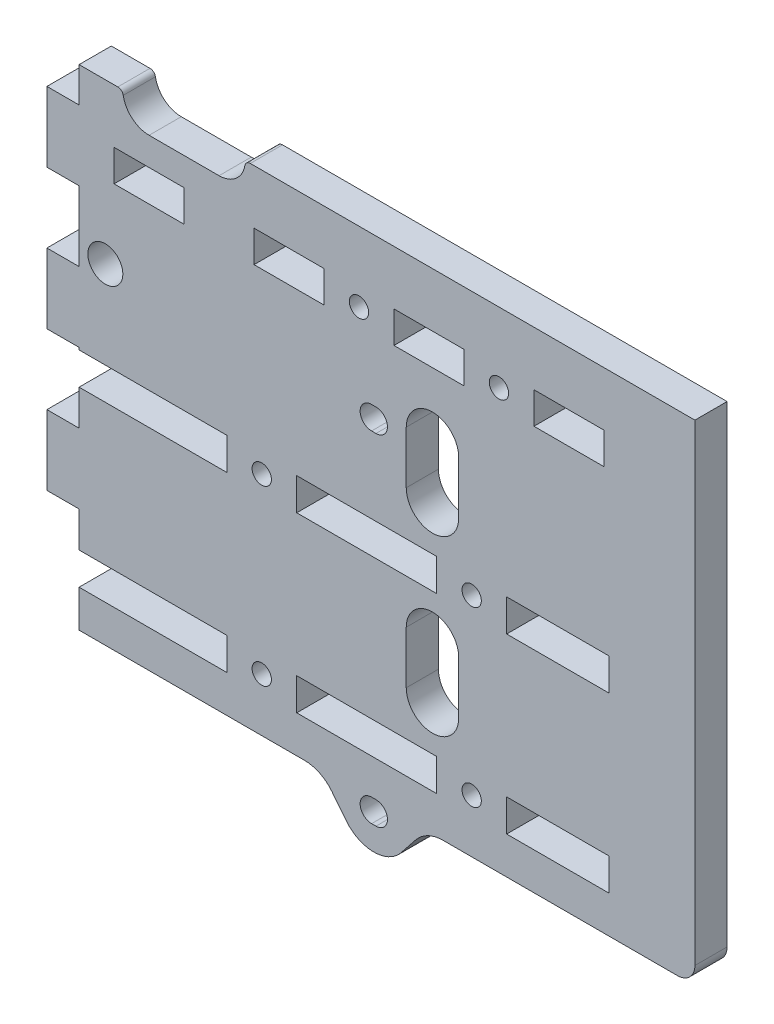
SolidWorks part; units mm, degrees
ref_plane "Front Plane" through (0, 0, 0) normal (0, 0, 1) x (1, 0, 0)
ref_plane "Top Plane" through (0, 0, 0) normal (0, 1, 0) x (1, 0, 0)
ref_plane "Right Plane" through (0, 0, 0) normal (1, 0, 0) x (0, 0, -1)
sketch "Sketch1" plane through (0, 0, 0) normal (0, 0, 1) x (1, 0, 0)
  line L0 (-61.722, 0) -> (-61.722, 12.7)
  line L1 (55.88, -44.45) -> (7.1279, -44.45)
  line L2 (55.88, -44.45) -> (55.88, 44.45)
  line L3 (55.88, 44.45) -> (-55.88, 44.45)
  line L4 (-55.88, -44.45) -> (-55.88, -37.692)
  line L5 (55.88, -44.45) -> (-55.88, 44.45) construction
  line L6 (55.88, 44.45) -> (-55.88, -44.45) construction
  line L7 (-61.722, 25.4) -> (-55.88, 25.4)
  line L8 (-61.722, 25.4) -> (-61.722, 38.1)
  line L9 (-61.722, 38.1) -> (-55.88, 38.1)
  line L10 (-55.88, 12.7) -> (-55.88, 25.4)
  line L11 (-61.722, 25.4) -> (-55.88, 38.1) construction
  line L12 (-61.722, 38.1) -> (-55.88, 25.4) construction
  line L13 (-61.722, 12.7) -> (-55.88, 12.7)
  line L14 (-61.722, 0) -> (-55.88, 0)
  line L15 (-61.722, -25.4) -> (-61.722, -12.7)
  line L16 (-61.722, -12.7) -> (-55.88, -12.7)
  line L17 (-61.722, -25.4) -> (-55.88, -25.4)
  line L18 (-61.722, 12.7) -> (-55.88, 0) construction
  line L19 (-61.722, 0) -> (-55.88, 12.7) construction
  line L20 (-61.722, -12.7) -> (-55.88, -25.4) construction
  line L21 (-61.722, -25.4) -> (-55.88, -12.7) construction
  line L22 (-55.88, 38.1) -> (-55.88, 44.45)
  line L23 (-55.88, -12.7) -> (-55.88, -6.25)
  line L24 (-55.88, -6.25) -> (55.88, -6.25) construction
  line L25 (-55.88, -31.85) -> (55.88, -31.85) construction
  line L26 (-58.801, -19.05) -> (-55.88, -19.05) construction
  line L27 (-55.88, -31.85) -> (-55.88, -6.25) construction
  line L28 (-55.88, -0.408) -> (-55.88, 0)
  line L29 (-29.083, -0.408) -> (-55.88, -0.408)
  line L30 (-29.083, -0.408) -> (-29.083, -6.25)
  line L31 (-29.083, -6.25) -> (-55.88, -6.25)
  line L32 (-58.801, -19.05) -> (55.88, -19.05) construction
  line L33 (-29.083, -0.408) -> (-55.88, -6.25) construction
  line L34 (-29.083, -6.25) -> (-55.88, -0.408) construction
  line L35 (9.017, -0.408) -> (-10.541, -0.408)
  line L36 (9.017, -0.408) -> (9.017, -6.25)
  line L37 (9.017, -6.25) -> (-10.541, -6.25)
  line L38 (27.559, -0.408) -> (21.717, -0.408)
  line L39 (9.017, -0.408) -> (-10.541, -6.25) construction
  line L40 (9.017, -6.25) -> (-10.541, -0.408) construction
  line L41 (40.259, -0.408) -> (27.559, -0.408)
  line L42 (40.259, -0.408) -> (40.259, -6.25)
  line L43 (40.259, -6.25) -> (27.559, -6.25)
  line L44 (-29.083, -37.692) -> (-55.88, -31.85) construction
  line L45 (40.259, -0.408) -> (27.559, -6.25) construction
  line L46 (40.259, -6.25) -> (27.559, -0.408) construction
  line L47 (-10.541, -0.408) -> (-16.383, -0.408)
  line L48 (-29.083, -31.85) -> (-55.88, -37.692) construction
  line L49 (-10.541, -6.25) -> (-16.383, -6.25)
  line L50 (-16.383, -0.408) -> (-16.383, -6.25)
  line L51 (27.559, -6.25) -> (21.717, -6.25)
  line L52 (21.717, -0.408) -> (21.717, -6.25)
  line L53 (-29.083, -31.85) -> (-55.88, -31.85)
  line L54 (-29.083, -37.692) -> (-55.88, -37.692)
  line L55 (40.259, -31.85) -> (27.559, -37.692) construction
  line L56 (40.259, -37.692) -> (27.559, -31.85) construction
  line L57 (9.017, -31.85) -> (-10.541, -37.692) construction
  line L58 (9.017, -37.692) -> (-10.541, -31.85) construction
  line L59 (21.717, -37.692) -> (21.717, -31.85)
  line L60 (27.559, -31.85) -> (21.717, -31.85)
  line L61 (-16.383, -37.692) -> (-16.383, -31.85)
  line L62 (-10.541, -31.85) -> (-16.383, -31.85)
  line L63 (-10.541, -37.692) -> (-16.383, -37.692)
  line L64 (40.259, -31.85) -> (27.559, -31.85)
  line L65 (40.259, -37.692) -> (40.259, -31.85)
  line L66 (40.259, -37.692) -> (27.559, -37.692)
  line L67 (27.559, -37.692) -> (21.717, -37.692)
  line L68 (9.017, -31.85) -> (-10.541, -31.85)
  line L69 (9.017, -37.692) -> (9.017, -31.85)
  line L70 (9.017, -37.692) -> (-10.541, -37.692)
  line L71 (-29.083, -37.692) -> (-29.083, -31.85)
  line L72 (-55.88, -31.85) -> (-55.88, -25.4)
  line L73 (-29.083, -3.329) -> (-16.383, -3.329) construction
  line L74 (21.717, -3.329) -> (9.017, -3.329) construction
  line L75 (21.717, -34.771) -> (9.017, -34.771) construction
  line L76 (-29.083, -34.771) -> (-16.383, -34.771) construction
  line L77 (-2.794, -46.228) -> (-2.0002, -46.228) construction
  line L78 (-2.794, -44.1452) -> (-2.0002, -44.1452)
  line L79 (-2.794, -48.3108) -> (-2.0002, -48.3108)
  line L80 (-11.9221, -44.45) -> (-55.88, -44.45)
  line L81 (-11.9221, -44.45) -> (-7.368, -50.1793)
  line L82 (7.1279, -44.45) -> (2.5738, -50.1793)
  line L83 (-2.794, 15.494) -> (-2.0002, 15.494) construction
  line L84 (-2.794, 17.5768) -> (-2.0002, 17.5768)
  line L85 (-2.794, 13.4112) -> (-2.0002, 13.4112)
  line L86 (-55.88, 31.75) -> (-11.43, 31.75) construction
  line L87 (-11.43, 28.879) -> (-11.43, 34.621)
  line L88 (-36.83, 28.879) -> (-49.53, 28.879)
  line L89 (-36.83, 28.879) -> (-36.83, 34.621)
  line L90 (-36.83, 34.621) -> (-49.53, 34.621)
  line L91 (-49.53, 28.879) -> (-49.53, 34.621)
  line L92 (-36.83, 28.879) -> (-49.53, 34.621) construction
  line L93 (-36.83, 34.621) -> (-49.53, 28.879) construction
  line L94 (-11.43, 28.879) -> (-24.13, 28.879)
  line L95 (-11.43, 34.621) -> (-24.13, 28.879) construction
  line L96 (-11.43, 28.879) -> (-24.13, 34.621) construction
  line L97 (-24.13, 28.879) -> (-24.13, 34.621)
  line L98 (-11.43, 34.621) -> (-24.13, 34.621)
  line L99 (13.97, 28.879) -> (13.97, 34.621)
  line L100 (13.97, 28.879) -> (1.27, 28.879)
  line L101 (13.97, 34.621) -> (1.27, 28.879) construction
  line L102 (13.97, 28.879) -> (1.27, 34.621) construction
  line L103 (1.27, 28.879) -> (1.27, 34.621)
  line L104 (13.97, 34.621) -> (1.27, 34.621)
  line L105 (39.37, 28.879) -> (39.37, 34.621)
  line L106 (39.37, 28.879) -> (26.67, 28.879)
  line L107 (39.37, 34.621) -> (26.67, 28.879) construction
  line L108 (39.37, 28.879) -> (26.67, 34.621) construction
  line L109 (26.67, 28.879) -> (26.67, 34.621)
  line L110 (39.37, 34.621) -> (26.67, 34.621)
  line L111 (26.67, 31.75) -> (55.88, 31.75) construction
  line L112 (1.27, 31.75) -> (13.97, 31.75) construction
  line L113 (-11.43, 31.75) -> (1.27, 31.75) construction
  line L114 (13.97, 31.75) -> (26.67, 31.75) construction
  circle A0 centre (-22.733, -3.329) radius 1.7526
  circle A1 centre (15.367, -3.329) radius 1.7526
  circle A2 centre (15.367, -34.771) radius 1.7526
  circle A3 centre (-22.733, -34.771) radius 1.7526
  arc A4 (-7.368, -50.1793) -> (2.5738, -50.1793) centre (-2.3971, -46.228) ccw
  arc A5 (-2.794, -44.1452) -> (-2.794, -48.3108) centre (-2.794, -46.228) ccw
  arc A6 (-2.0002, -48.3108) -> (-2.0002, -44.1452) centre (-2.0002, -46.228) ccw
  arc A7 (-2.794, 17.5768) -> (-2.794, 13.4112) centre (-2.794, 15.494) ccw
  arc A8 (-2.0002, 13.4112) -> (-2.0002, 17.5768) centre (-2.0002, 15.494) ccw
  circle A9 centre (-5.08, 31.75) radius 1.7526
  circle A10 centre (20.32, 31.75) radius 1.7526
  point P0 (0, 0)
  point P6 (-58.801, 31.75)
  point P20 (-58.801, 6.35)
  point P28 (-58.801, -19.05)
  point P35 (-42.4815, -3.329)
  point P36 (-0.762, -3.329)
  point P44 (33.909, -3.329)
  point P69 (33.909, -34.771)
  point P70 (-0.762, -34.771)
  point P71 (-42.4815, -34.771)
  point P72 (0, -38.1)
  point P93 (-2.3971, -46.228)
  point P104 (-2.3971, 15.494)
  point P110 (-43.18, 31.75)
  dimension "D14" = 3.5052
  dimension "D18" = 2.0828
  dimension "D22" = 12.7
  dimension "D31" = 3.5052
  dimension "D32" = 3.5052
  dimension "D1" = 12.7
  dimension "D2" = 5.842
  dimension "D3" = 12.7
  dimension "D6" = 25.4
  dimension "D7" = 111.76
  dimension "D8" = 25.6
  dimension "D9" = 5.842
  dimension "D10" = 26.797
  dimension "D11" = 5.842
  dimension "D12" = 5.842
  dimension "D13" = 19.558
  dimension "D15" = 12.7
  dimension "D16" = 5.842
  dimension "D19" = 90.678
  dimension "D20" = 53.086
  dimension "D21" = 0.7937
  dimension "D23" = 9.525
  dimension "D24" = 9.525
  dimension "D26" = 12.7
  dimension "D27" = 12.7
  dimension "D28" = 5.742
  dimension "D29" = 12.7
  dimension "D4" = 3
  dimension "D5" = 3
  dimension "D17" = 2
  dimension "D25" = 2
  dimension "D30" = 4
extrude "Boss-Extrude1" add sketch "Sketch1" along normal blind 5.842
sketch "Sketch2" plane through (0, 0, 5.842) normal (0, 0, 1) x (1, 0, 0)
  line L0 (55.88, 44.45) -> (-55.88, 44.45) construction
  line L1 (-55.88, 25.4) -> (-55.88, 12.7) construction
  circle A0 centre (-51.1175, 15.494) radius 3.175
  dimension "D1" = 6.35
  dimension "D2" = 28.956
  dimension "D3" = 4.7625
extrude "Cut-Extrude1" cut sketch "Sketch2" against normal through all
fillet "Fillet1" radius 6.35 2 edges at (7.1279, -44.45, 2.921) (-11.9221, -44.45, 2.921)
sketch "Sketch4" plane through (0, 0, 5.842) normal (0, 0, 1) x (1, 0, 0)
  line L0 (-43.18, 44.45) -> (-30.48, 44.45) construction
  line L1 (55.88, 44.45) -> (-55.88, 44.45) construction
  line L2 (-43.18, 49.2125) -> (-30.48, 49.2125)
  line L3 (-43.18, 39.6875) -> (-30.48, 39.6875)
  line L4 (-55.88, 44.45) -> (-55.88, 38.1) construction
  arc A0 (-43.18, 49.2125) -> (-43.18, 39.6875) centre (-43.18, 44.45) ccw
  arc A1 (-30.48, 39.6875) -> (-30.48, 49.2125) centre (-30.48, 44.45) ccw
  point P4 (-36.83, 44.45)
  dimension "D2" = 4.7625
  dimension "D1" = 12.7
  dimension "D3" = 19.05
extrude "Cut-Extrude2" cut sketch "Sketch4" against normal through all
fillet "Fillet2" radius 1 2 edges at (-25.7175, 44.45, 2.921) (-47.9425, 44.45, 2.921)
fillet "Fillet3" radius 3.175 1 edges at (55.88, -44.45, 2.921)
sketch "Sketch5" plane through (0, 0, 5.842) normal (0, 0, 1) x (1, 0, 0)
  line L0 (-61.722, -19.05) -> (55.88, -19.05) construction
  line L1 (8.255, -23.8125) -> (8.255, -14.2875) construction
  line L2 (3.4925, -23.8125) -> (3.4925, -14.2875)
  line L3 (13.0175, -23.8125) -> (13.0175, -14.2875)
  line L4 (-61.722, -12.7) -> (-61.722, -25.4) construction
  line L5 (55.88, -41.275) -> (55.88, 44.45) construction
  line L6 (9.017, -3.329) -> (15.367, -3.329) construction
  line L7 (9.017, -6.25) -> (9.017, -0.408) construction
  line L8 (-61.722, 12.392) -> (55.88, 12.392) construction
  line L9 (8.255, 17.1545) -> (8.255, 7.6295) construction
  line L10 (3.4925, 17.1545) -> (3.4925, 7.6295)
  line L11 (13.0175, 17.1545) -> (13.0175, 7.6295)
  arc A0 (3.4925, -23.8125) -> (13.0175, -23.8125) centre (8.255, -23.8125) ccw
  arc A1 (13.0175, -14.2875) -> (3.4925, -14.2875) centre (8.255, -14.2875) ccw
  arc A2 (3.4925, 17.1545) -> (13.0175, 17.1545) centre (8.255, 17.1545) cw
  arc A3 (13.0175, 7.6295) -> (3.4925, 7.6295) centre (8.255, 7.6295) cw
  point P6 (8.255, -19.05)
  point P24 (8.255, 12.392)
  dimension "D2" = 4.7625
  dimension "D1" = 9.525
  dimension "D3" = 47.625
extrude "Cut-Extrude3" cut sketch "Sketch5" against normal through all
